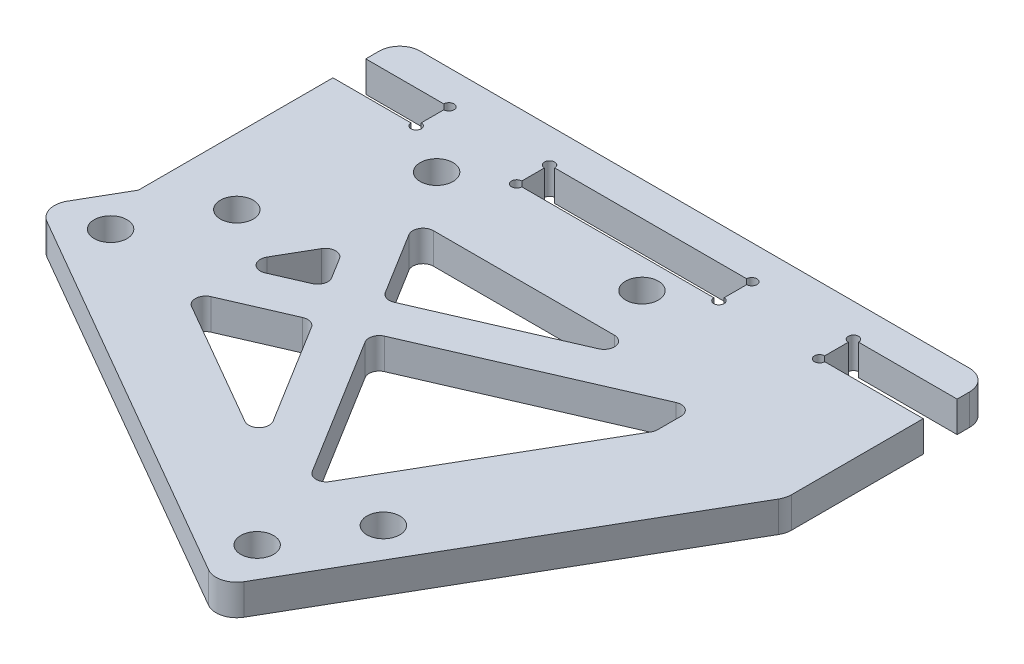
SolidWorks part; units mm, degrees
material "Thornel Mat VMA"
ref_plane "Front Plane" through (0, 0, 0) normal (0, 0, 1) x (1, 0, 0)
ref_plane "Top Plane" through (0, 0, 0) normal (0, 1, 0) x (1, 0, 0)
ref_plane "Right Plane" through (0, 0, 0) normal (1, 0, 0) x (0, 0, -1)
other "Configuration Table"
sketch "Sketch1" plane through (0, 0, 0) normal (0, 1, 0) x (1, 0, 0)
  line L1 (-13, 9.4081) -> (44.5, 9.4081)
  line L2 (-13, 9.4081) -> (-13, 6)
  line L3 (-13, 6) -> (44.5, 6)
  line L4 (44.5, 9.4081) -> (44.5, 6)
  line L5 (-5, 6) -> (5, 6)
  line L6 (-5, 6) -> (-5, 3)
  line L7 (-5, 3) -> (5, 3)
  line L8 (5, 6) -> (5, 3)
  line L9 (24.5, 6) -> (34.5, 6)
  line L10 (24.5, 6) -> (24.5, 3)
  line L11 (24.5, 3) -> (34.5, 3)
  line L12 (34.5, 6) -> (34.5, 3)
  line L13 (-13, 3) -> (44.5, 3)
  line L14 (-13, 3) -> (-13, -21.8465)
  line L15 (-13, -21.8465) -> (44.5, -21.8465)
  line L16 (44.5, 3) -> (44.5, -21.8465)
  point P13 (39.5196, -25.118)
  point P14 (-13, -21.8465)
  line B0 (-5, 3) -> (-5, 6)
  line B1 (5, 3) -> (5, 6)
  line B2 (24.5, 3) -> (24.5, 6)
  line B3 (34.5, 3) -> (34.5, 6)
  circle B4 centre (20, 0) radius 1.6
  circle B5 centre (0, 0) radius 1.6
  dimension "D1" = 10
  dimension "D2" = 8
sketch_block_instance "Block5-1"
sketch_block "Block5"
extrude "Boss-Extrude1" add sketch "Sketch1" along normal blind 3 contours L4 L1 L2 L3 | L8 L3 L6 L7 | L12 L3 L10 L11 | L16 L13 L11 L7 L14 L15 B5 B4 region at (15.75, 0, -7.7041) region at (0, 0, -4.5) region at (29.5, 0, -4.5) region at (15.8155, 0, 9.5305)
sketch "Sketch3" plane through (0, 3, 0) normal (0, 1, 0) x (1, 0, 0)
  line L0 (-13, 9.4081) -> (-13, 6) construction
  line L1 (-13, 6.1) -> (-4.9, 6.1)
  line L2 (-13, 6.1) -> (-13, 2.9)
  line L3 (-13, 2.9) -> (-4.9, 2.9)
  line L4 (-4.9, 6.1) -> (-4.9, 2.9)
  line L5 (44.5, 9.4081) -> (44.5, 6) construction
  line L6 (44.5, 6.2) -> (34.4, 6.2)
  line L7 (44.5, 6.2) -> (44.5, 2.9)
  line L8 (44.5, 2.9) -> (34.4, 2.9)
  line L9 (34.4, 6.2) -> (34.4, 2.9)
  line L10 (34.5, 6) -> (44.5, 6) construction
  line L11 (34.5, 3) -> (44.5, 3) construction
  line L12 (34.5, 6) -> (34.5, 3) construction
  line L13 (-13, 6) -> (-5, 6) construction
  line L14 (-13, 3) -> (-5, 3) construction
  line L15 (-5, 6) -> (-5, 3) construction
  line L16 (24.6, 6.1) -> (4.9, 6.1)
  line L17 (4.9, 6.1) -> (4.9, 2.9)
  line L18 (4.9, 2.9) -> (24.6, 2.9)
  line L19 (24.6, 2.9) -> (24.6, 6.1)
  line L20 (24.5, 3) -> (24.5, 6)
  line L21 (5, 3) -> (24.5, 3)
  line L22 (5, 6) -> (5, 3)
  line L23 (24.5, 6) -> (5, 6)
  line L24 (24.5, 3) -> (24.5, 6)
  line L25 (5, 3) -> (24.5, 3)
  line L26 (5, 6) -> (5, 3)
  line L27 (24.5, 6) -> (5, 6)
  dimension "D1" = 0.2
  dimension "D2" = 0.1
  dimension "D3" = 0.1
  dimension "D4" = 0.1
  dimension "D5" = 0.1
  dimension "D6" = 0.1
  dimension "D7" = 0
  dimension "D8" = 0.1
extrude "Cut-Extrude1" cut sketch "Sketch3" against normal blind 3
sketch "Sketch4" plane through (0, 3, 0) normal (0, 1, 0) x (1, 0, 0)
  line L0 (24.6, 2.9) -> (24.6, 6.1) construction
  line L1 (24.6, 6.1) -> (4.9, 6.1) construction
  circle A0 centre (-4.9, 6.1) radius 0.5
  circle A1 centre (-4.9, 2.9) radius 0.5
  circle A2 centre (4.9, 6.1) radius 0.5
  circle A3 centre (4.9, 2.9) radius 0.5
  circle A4 centre (24.6, 6.1) radius 0.5
  circle A5 centre (24.6, 2.9) radius 0.5
  circle A6 centre (34.4, 2.9) radius 0.5
  circle A7 centre (34.4, 6.2) radius 0.5
  dimension "D1" = 1
extrude "Cut-Extrude2" cut sketch "Sketch4" against normal blind 3
sketch "Sketch5" plane through (0, 3, 0) normal (0, 1, 0) x (1, 0, 0)
  point P2 (-8.5281, 28.6583)
  point P3 (0, -6.1548)
  point P4 (0, 0)
  point P6 (20, 0)
  circle B0 centre (22.7128, -40.1945) radius 2.4 construction
  circle B1 centre (27.2128, -32.4003) radius 2.4 construction
  circle B2 centre (-11.0621, -20.6945) radius 2.4 construction
  circle B3 centre (-11.0621, -20.6945) radius 2.5 construction
  circle B4 centre (-6.5621, -12.9003) radius 2.5 construction
  circle B5 centre (0, 0) radius 1.6
  circle B6 centre (20, 0) radius 1.6
sketch_block_instance "Block6-1"
sketch_block "Block6"
sketch "Sketch6" plane through (0, 3, 0) normal (0, 1, 0) x (1, 0, 0)
  line L0 (-6.1767, -4.2328) -> (37.9249, -21.8465)
  line L1 (-13, -21.8465) -> (44.5, -21.8465) construction
  line L2 (37.9249, -21.8465) -> (24.1769, -45.6586)
  line L3 (24.1769, -45.6586) -> (-16.5262, -22.1586)
  line L4 (-16.5262, -22.1586) -> (-6.1767, -4.2328)
  line L5 (-11.0621, -20.6945) -> (22.7128, -40.1945) construction
  line L6 (22.7128, -40.1945) -> (27.2128, -32.4003) construction
  circle A0 centre (22.7128, -40.1945) radius 1.6
  circle A1 centre (27.2128, -32.4003) radius 1.6
  circle A2 centre (-11.0621, -20.6945) radius 1.6
  circle A3 centre (-6.5621, -12.9003) radius 1.6
  point P18 (36.4013, -24.685)
  line M17 (-13, -21.8465) -> (44.5, -21.8465)
  dimension "D1" = 3.2
  dimension "D2" = 4
  dimension "D3" = 4
  dimension "D4" = 4
extrude "Boss-Extrude2" add sketch "Sketch6" against normal blind 3
extrude "Cut-Extrude3" cut sketch "Sketch6<2>" against normal blind 3 contours A3 | A2 M17 region at (-11.0621, 3, 20.5705) region at (-6.5621, 3, 12.9003)
sketch "Sketch6<2>" plane through (0, 3, 0) normal (0, 1, 0) x (1, 0, 0) same geometry as "Sketch6"
sketch "Sketch8" plane through (0, 3, 0) normal (0, 1, 0) x (1, 0, 0)
  line L0 (37.9249, -21.8465) -> (47.1522, -5.8644)
  line L1 (47.1522, -5.8644) -> (51.9523, -20.7656)
  line L2 (51.9523, -20.7656) -> (44.5, -26.0591)
  line L3 (44.5, -26.0591) -> (37.9249, -21.8465)
  line L4 (24.1769, -45.6586) -> (37.9249, -21.8465) construction
extrude "Cut-Extrude4" cut sketch "Sketch8" against normal blind 3
fillet "Fillet1" radius 2 5 edges at (44.5, 1.5, 10.4581) (44.5, 1.5, -9.4081) (-13, 1.5, -9.4081) (24.1769, 1.5, 45.6586) (-16.5262, 1.5, 22.1586)
sketch "Sketch9" plane through (0, 3, 0) normal (0, 1, 0) x (1, 0, 0)
  line L1 (1, -5.1) -> (32.5, -5.1)
  line L2 (32.5, -5.1) -> (32.5, -11.2427)
  line L3 (32.5, -11.2427) -> (19.0167, -34.5965)
  line L4 (19.0167, -34.5965) -> (-4.366, -21.0965)
  line L5 (-14.7942, -23.1586) -> (22.4449, -44.6586) construction
  line L6 (25.1769, -43.9266) -> (44.2321, -10.9222) construction
  line L7 (44.5, 2.9) -> (44.5, -9.9222) construction
  line L8 (-4.366, -21.0965) -> (1, -11.8023)
  line L9 (1, -11.8023) -> (1, -5.1)
  line L10 (-13, 2.9) -> (-13, -16.051) construction
  line L11 (-13, -16.051) -> (-15.5262, -20.4266) construction
  line L12 (5.4, 2.9) -> (24.1, 2.9) construction
  point P16 (31.0449, -11.8809)
  dimension "D1" = 7
  dimension "D2" = 10
  dimension "D3" = 10
  dimension "D4" = 14
  dimension "D5" = 8
  dimension "D6" = 12
extrude "Cut-Extrude5" cut sketch "Sketch9" against normal blind 3
sketch "Sketch10" plane through (0, 3, 0) normal (0, 1, 0) x (1, 0, 0)
  line L0 (-4.8262, -21.2041) -> (33.1483, -4.7038)
  line L1 (0.3899, -4.7038) -> (19.3096, -35.2992)
  point P4 (33.1483, -4.7038)
  point P6 (32.482, -11.2739)
extrude "Extrude-Thin1" add sketch "Sketch10" against normal up to surface (3 mm away) thin up to face at (13.6084, 0, 14.823) thin type mid plane wall 4
fillet "Fillet2" radius 1 13 edges at (15.1391, 1.5, 32.3577) (-2.3022, 1.5, 22.288) (6.5371, 1.5, 18.4473) (10.2441, 1.5, 16.8366) (20.0837, 1.5, 32.7484) (32.5, 1.5, 11.2427) (32.5, 1.5, 7.1662) (27.2179, 1.5, 5.1) (8.1183, 1.5, 13.3989) (2.9864, 1.5, 5.1) (1, 1.5, 11.8023) (4.4113, 1.5, 15.0097) (-2.6142, 1.5, 18.0623)
sketch "Sketch11" plane through (0, 3, 0) normal (0, 1, 0) x (1, 0, 0)
  line L0 (0.8149, -12.1229) -> (2.2716, -9.5998)
  line L1 (0.866, -12.0343) -> (-1.0986, -15.4371) construction
  line L2 (2.2716, -9.5998) -> (-0.5086, -8.5144)
  line L3 (-0.5086, -8.5144) -> (0.8149, -12.1229)
extrude "Boss-Extrude3" add sketch "Sketch11" against normal up to surface (3 mm away) up to face at (23.8381, 0, 16.9686)
fillet "Fillet3" radius 1 1 edges at (1.6895, 1.5, 10.6081)
